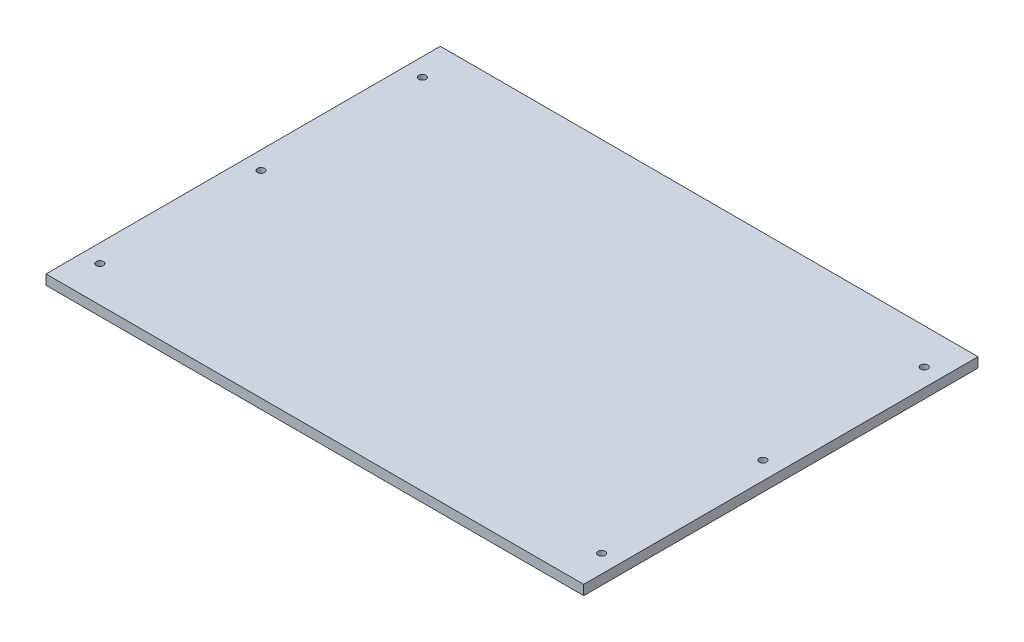
SolidWorks part; units mm, degrees
ref_plane "Front Plane" through (0, 0, 0) normal (0, 0, 1) x (1, 0, 0)
ref_plane "Top Plane" through (0, 0, 0) normal (0, 1, 0) x (1, 0, 0)
ref_plane "Right Plane" through (0, 0, 0) normal (1, 0, 0) x (0, 0, -1)
sketch "Sketch1" plane through (0, 0, 0) normal (0, 0, 1) x (1, 0, 0)
  line L0 (0, 0) -> (30, 0)
  line L1 (30, 25.5) -> (30, -5.5) construction
  line L2 (30, 0) -> (30, -3.5)
  line L3 (30, -3.5) -> (270, -3.5)
  line L4 (270, -3.5) -> (270, 0)
  line L5 (270, -5) -> (270, 25) construction
  line L6 (270, 0) -> (300, 0)
  line L7 (300, 0.5) -> (300, 6.87) construction
  line L8 (293.13, 0) -> (299.5, 0) construction
  line L9 (0, 0) -> (0, -2)
  line L10 (0, -2) -> (28, -2)
  line L11 (28, -2) -> (28, -5.5)
  line L12 (28, -5.5) -> (272, -5.5)
  line L13 (272, -5.5) -> (272, -2)
  line L14 (272, -2) -> (300, -2)
  line L15 (300, -2) -> (300, 0)
  point P23 (0, 0)
  dimension "D1" = 2
  dimension "D2" = 2
  dimension "D3" = 2
  dimension "D4" = 2
  dimension "D5" = 2
sketch "Sketch2" plane through (0, 0, 0) normal (0, 0, 1) x (1, 0, 0)
  line L0 (300, -2) -> (300, 0) construction
  line L1 (0, 0) -> (300, 0)
  line L2 (0, 0) -> (0, -5.5)
  line L3 (0, -5.5) -> (300, -5.5)
  line L4 (300, 0) -> (300, -5.5)
  line L5 (28, -5.5) -> (272, -5.5) construction
extrude "Boss-Extrude1" add sketch "Sketch2" along normal mid plane 220
sketch "Sketch3" plane through (0, -5.5, 0) normal (0, -1, 0) x (1, 0, 0)
  line L0 (10, 110) -> (10, -110) construction
  line L1 (0, 110) -> (300, 110) construction
  line L2 (0, -110) -> (300, -110) construction
  line L3 (0, 110) -> (0, -110) construction
  line L5 (150, 110) -> (150, -110) construction
  circle A0 centre (10, 90) radius 2
  circle A1 centre (10, -90) radius 2
  circle A2 centre (10, 0) radius 2
  circle A3 centre (290, -90) radius 2
  circle A4 centre (290, 0) radius 2
  circle A5 centre (290, 90) radius 2
  dimension "D2" = 4
  dimension "D4" = 20
  dimension "D1" = 10
  dimension "D3" = 20
extrude "Cut-Extrude1" cut sketch "Sketch3" against normal through all
